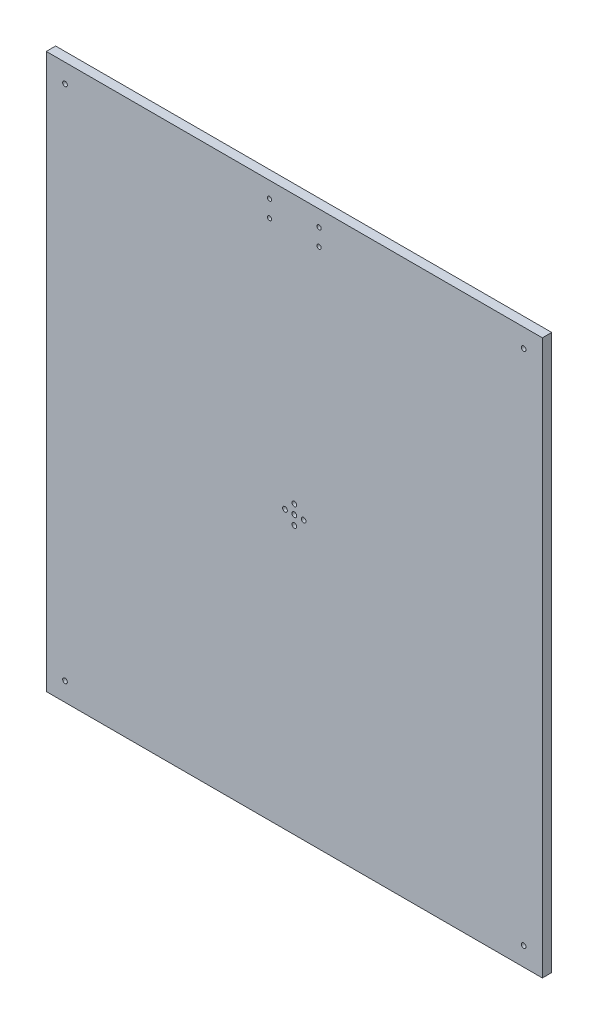
SolidWorks part; units mm, degrees
ref_plane "Спереди" through (0, 0, 0) normal (0, 0, 1) x (1, 0, 0)
ref_plane "Сверху" through (0, 0, 0) normal (0, 1, 0) x (1, 0, 0)
ref_plane "Справа" through (0, 0, 0) normal (1, 0, 0) x (0, 0, -1)
sketch "Эскиз3" plane through (0, 0, 0) normal (0, 0, 1) x (1, 0, 0)
  line L0 (0, 0) -> (0, 10) construction
  line L5 (265, -296.15) -> (-265, -296.15)
  line L6 (265, -296.15) -> (265, 296.15)
  line L7 (265, 296.15) -> (-265, 296.15)
  line L8 (-265, -296.15) -> (-265, 296.15)
  line L9 (0, 0) -> (10, 0) construction
  line L10 (0, 0) -> (0, -10) construction
  line L11 (0, 0) -> (-10, 0) construction
  circle A0 centre (0, 0) radius 2.55
  circle A1 centre (0, 10) radius 2.55
  circle A2 centre (10, 0) radius 2.55
  circle A3 centre (0, -10) radius 2.55
  circle A4 centre (-10, 0) radius 2.55
  point P0 (0, 0)
  point P5 (-265, 0)
  point P6 (0, 296.15)
  point P21 (0, 0)
  dimension "D3" = 5.1
  dimension "D4" = 5.1
  dimension "D1" = 592.3
  dimension "D2" = 530
  dimension "D5" = 10
  dimension "D6" = 4
extrude "Бобышка-Вытянуть1" add sketch "Эскиз3" along normal blind 10
sketch "Эскиз4" plane through (0, 0, 10) normal (0, 0, 1) x (1, 0, 0)
  line L0 (265, 296.15) -> (-265, 296.15) construction
  line L1 (-265, 296.15) -> (-265, -296.15) construction
  circle A0 centre (-245, 276.15) radius 2.5
  dimension "D1" = 5
  dimension "D2" = 20
  dimension "D3" = 20
extrude "Вырез-Вытянуть1" cut sketch "Эскиз4" against normal through all contours A0
pattern_linear "Линейный массив1" count 2 spacing 490 along (1, 0, 0) count 2 spacing 552.3 along (0, -1, 0) of "Вырез-Вытянуть1"
sketch "Эскиз7" plane through (0, 0, 0) normal (0, 0, -1) x (-1, 0, 0)
  line L9 (-26.5, 279.15) -> (26.5, 279.15) construction
  line L10 (-26.5, 279.15) -> (-26.5, 261.15) construction
  line L11 (-26.5, 261.15) -> (26.5, 261.15) construction
  line L16 (26.5, 279.15) -> (26.5, 261.15) construction
  line L17 (-265, 296.15) -> (265, 296.15) construction
  circle A0 centre (-26.5, 279.15) radius 2.25
  circle A1 centre (26.5, 279.15) radius 2.25
  circle A2 centre (-26.5, 261.15) radius 2.25
  circle A3 centre (26.5, 261.15) radius 2.25
  point P4 (0, 261.15)
  dimension "D4" = 4.5
  dimension "D5" = 4.5
  dimension "D6" = 4.5
  dimension "D7" = 4.5
  dimension "D1" = 53
  dimension "D2" = 18
  dimension "D3" = 17
extrude "Вырез-Вытянуть2" cut sketch "Эскиз7" against normal through all
equation "\"Ширина груза\"= 420"
equation "\"Глубина груза\"= 490"
equation "\"Высота груза\"= 297"
equation "\"Ширина ячейки\"= \"Ширина груза\" + 10"
equation "\"Глубина ячейки\"= \"Глубина груза\" + 10"
equation "\"Высота ячейки\"= \"Высота груза\" + 10 + 13"
equation "\"Колво ячеек ширина\"= 2"
equation "\"Колво ячеек высота\"= 2"
equation "\"Толщина стенки\"= 10"
equation "\"Крепление дверцы\"= 5"
equation "\"Ширина рейки\"= \"Толщина шестерни\""
equation "\"Высота рейки\"= 20"
equation "\"Высота пола\"= 20"
equation "\"Колво полозьев\"= 5"
equation "\"Отступ рейки\"= 20"
equation "\"Глубина каретки\"= \"Глубина ячейки\" + 30 + \"Мотор Y высота корпуса\" + 20"
equation "\"Длинна рейки\"= ( \"Ширина ячейки\" + \"Толщина стенки\" + \"Крепление дверцы\" ) * \"Колво ячеек ширина\" + \"Ширина ячейки выгрузки\" * \"Колво выгрузки\" + \"Толщина стенки\""
equation "\"Отступ шпильки\"= 20"
equation "\"Диаметр шпильки\"= 5"
equation "\"D1@Бобышка-Вытянуть1\" = \"Толщина стенки\""
equation "\"D1@Эскиз4\"= \"Диаметр шпильки\""
equation "\"D2@Эскиз4\"=\"Отступ шпильки\""
equation "\"D3@Эскиз4\"= \"Отступ шпильки\""
equation "\"D2@Эскиз3\"=\"Ширина ячейки\" + \"Ширина пластины\" * 2"
equation "\"D1@Эскиз3\"=\"Глубина каретки\" "
equation "\"D3@Линейный массив1\"=\"Ширина ячейки\"  +\"Ширина пластины\" *2 - \"Отступ шпильки\" * 2"
equation "\"D4@Линейный массив1\"=\"Глубина каретки\" + \"Ширина рейки\" * 2 - \"Отступ шпильки\" * 2 - \"Ширина рейки\" * 2"
equation "\"Длинна шпильки\"= ( \"Высота ячейки\" + \"Толщина стенки\" + \"Высота пола\" ) * \"Колво ячеек высота\" + ( \"Толщина стенки\" + \"Отступ рейки\" ) * 2 "
equation "\"Ширина пластины\"= 50  "
equation "\"Высота зона выгрузки\"= \"Высота ячейки\" * 2 + \"Толщина стенки\" * 2"
equation "\"Колво выгрузки\"= 1"
equation "\"Отступ крепления мотора фиксации\" = 30"
equation "\"Мотор X ширина корпуса\"= 42.3"
equation "\"Мотор X высота корпуса\"= 42.3"
equation "\"Мотор X длина корпуса\"= 40"
equation "\"Мотор X вылет вала\"= 19.8"
equation "\"Мотор Y ширина корпуса\"= 42.3"
equation "\"Мотор Y высота корпуса\"= 42.3"
equation "\"Мотор Y длина корпуса\"= 48"
equation "\"Мотор Y вылет вала\"= 30"
equation "\"Мотор Z ширина корпуса\"= 42"
equation "\"Мотор Z высота корпуса\"= 42"
equation "\"Мотор Z длина корпуса\"= 40"
equation "\"Мотор Z вылет вала\"= 23"
equation "\"Мотор диаметр вала ПРЕДВ\"= 5"
equation "\"Мотор шаг крепления ПРЕДВ\"= 31"
equation "\"Мотор диаметр отверстий ПРЕДВ\"= 3"
equation "\"Мотор глубина отверстий ПРЕДВ\"= 4.5"
equation "\"Мотор диаметр буртика ПРЕДВ\"= 22"
equation "\"Мотор высота буртика ПРЕДВ\"= 2"
equation "\"Мотор диаметр шкива ПРЕДВ\"= 16"
equation "\"Мотор длина шкива ПРЕДВ\"= 12"
equation "\"Мотор отступ шкива ПРЕДВ\"= 5"
equation "\"Мотор X шаг градусов\"= 1.8"
equation "\"Мотор Y шаг градусов\"= 1.8"
equation "\"Мотор Z шаг градусов\"= 1.8"
equation "\"Мотор Y диаметр ротора\"= 25.78"
equation "\"Толщина шестерни\"= 10"
equation "\"Ширина ячейки выгрузки\"= \"Ширина ячейки\" + \"Толщина стенки\" + \"Отступ крепления мотора фиксации\"*2"
